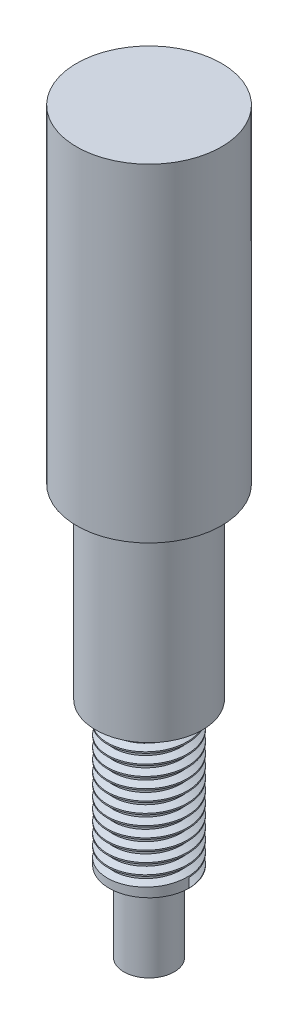
SolidWorks part; units mm, degrees
material "AISI 316 Annealed Stainless Steel Bar (SS)"
ref_plane "Front Plane" through (0, 0, 0) normal (0, 0, 1) x (1, 0, 0)
ref_plane "Top Plane" through (0, 0, 0) normal (0, 1, 0) x (1, 0, 0)
ref_plane "Right Plane" through (0, 0, 0) normal (1, 0, 0) x (0, 0, -1)
sketch "Sketch2" plane through (0, 0, 0) normal (0, 0, 1) x (1, 0, 0)
  line L0 (0, 0) -> (0, 508.8276) construction
  line L1 (0, 0) -> (6, 0)
  line L2 (0, 0) -> (0, 19.05)
  line L3 (0, 19.05) -> (6, 19.05)
  line L4 (6, 0) -> (6, 19.05)
  line L5 (0, 19.05) -> (9.525, 19.05)
  line L6 (0, 19.05) -> (0, 53.34)
  line L7 (0, 53.34) -> (9.525, 53.34)
  line L8 (9.525, 19.05) -> (9.525, 53.34)
  line L9 (0, 53.34) -> (12.721, 53.34)
  line L10 (0, 53.34) -> (0, 97.79)
  line L11 (0, 97.79) -> (12.721, 97.79)
  line L12 (12.721, 53.34) -> (12.721, 97.79)
  line L13 (0, 97.79) -> (17.272, 97.79)
  line L14 (0, 97.79) -> (0, 176.022)
  line L15 (0, 176.022) -> (17.272, 176.022)
  line L16 (17.272, 97.79) -> (17.272, 176.022)
  dimension "D1" = 78.232
  dimension "D2" = 17.272
  dimension "D4" = 44.45
  dimension "D3" = 12.721
  dimension "D5" = 34.29
  dimension "D6" = 9.525
  dimension "D7" = 19.05
  dimension "D8" = 6
revolve "Revolve1" add sketch "Sketch2" angle 360 about L0 region at (3, 9.525, 0) region at (4.7625, 36.195, 0) region at (6.3605, 75.565, 0) region at (8.636, 136.906, 0)
thread "Thread2" pitch 2.54 method cut profile "Thread Profile3" start angle 0, offset 0, length 0, pitch 2.54, diameter 19.05
ref_plane "Plane3" through (9.525, 19.05, 0) normal (0, 0, 1) x (1, 0, 0)
sketch "Thread Profile3" plane through (9.525, 19.05, 0) normal (0, 0, 1) x (1, 0, 0)
  line L0 (0, 0) -> (0, 2.54) construction
  line L11 (0, 0) -> (0, 2.2225)
  line L12 (0, 2.2225) -> (-1.3748, 1.4287)
  line L13 (-1.3748, 1.4287) -> (-1.3748, 0.7937)
  line L15 (-1.3748, 0.7937) -> (0, 0)
  line L17 (-1.3748, 1.1112) -> (0, 1.1112) construction
  point P2 (0, 0)
  dimension "Pitch" = 2.54
  dimension "Profile_Angle" = 60
  dimension "Profile_Land" = 0.635
  dimension "Profile_Height" = 1.3748
equation "\"hole diamiter\"= 1.36in"
equation "\"wheel depth\"= 2.88"
equation "\"press_tolerance\"= 0.00165"
equation "\"wheel_connection\"= \"hole diamiter\"'https://at-machining.com/tolerance-press-fit/"
equation "\"D1@Sketch2\"=\"wheel depth\"+0.2"
equation "\"D2@Sketch2\"=\"wheel_connection\"/2"
equation "\"fitting depth\"=1.75"
equation "\"D4@Sketch2\"=\"fitting depth\""
equation "\"bearing_id\"= 1"
equation "\"bearing_connection\"= \"bearing_id\" + \"press_tolerance\"'https://at-machining.com/tolerance-press-fit/"
equation "\"D3@Sketch2\"=\"bearing_connection\"/2"
equation "\"thread length\"= 1.35"
equation "\"major_diamiter\"= 0.75 'https://www.machiningdoctor.com/threadinfo/?tid=81"
equation "\"D5@Sketch2\"=\"thread length\""
equation "\"D6@Sketch2\"=\"major_diamiter\"/2"
equation "\"coupling diamiter\"= 12mm"
equation "\"coupling lenght\"= 1.5 / 2"
equation "\"D7@Sketch2\"=\"coupling lenght\""
equation "\"D8@Sketch2\"=\"coupling diamiter\"/2"
